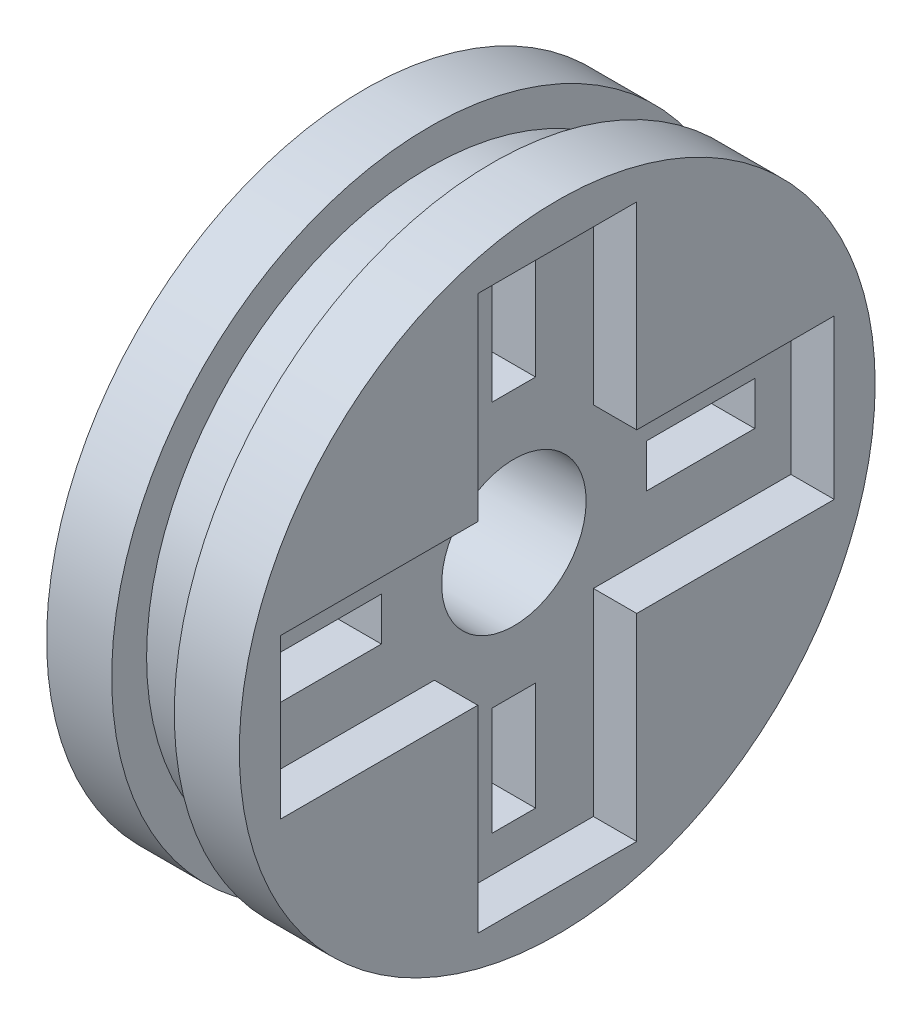
SolidWorks part; units mm, degrees
ref_plane "Front Plane" through (0, 0, 0) normal (0, 0, 1) x (1, 0, 0)
ref_plane "Top Plane" through (0, 0, 0) normal (0, 1, 0) x (1, 0, 0)
ref_plane "Right Plane" through (0, 0, 0) normal (1, 0, 0) x (0, 0, -1)
sketch "Sketch1" plane through (0, 0, 0) normal (1, 0, 0) x (0, 0, -1)
  circle A0 centre (52, -65) radius 13.2
extrude "Boss-Extrude1" add sketch "Sketch1" along normal blind 8 from offset 85.2 offset against normal yes
sketch "Sketch2" plane through (0, 0, 0) normal (1, 0, 0) x (0, 0, -1)
  circle A0 centre (52, -65) radius 20
extrude "Boss-Extrude2" add sketch "Sketch2" along normal blind 2.6 from offset 82.5 separate body offset against normal yes
combine bodies "Combine1" operation type subtract main body 101 bodies to subtract 102
sketch "Sketch3" plane through (0, 0, 0) normal (1, 0, 0) x (0, 0, -1)
  circle A0 centre (52, -65) radius 11.75
extrude "Boss-Extrude3" add sketch "Sketch3" along normal blind 2.6 from offset 82.5 offset against normal yes
sketch "Sketch4" plane through (0, 0, 0) normal (1, 0, 0) x (0, 0, -1)
  circle A0 centre (52, -65) radius 4.6
extrude "Boss-Extrude4" add sketch "Sketch4" along normal blind 2.3 from offset 79 separate body offset against normal yes
combine bodies "Combine2" operation type subtract main body 105 bodies to subtract 106
sketch "Sketch5" plane through (0, 0, 0) normal (0, 0, 1) x (1, 0, 0)
  line L1 (-79, -65) -> (-76.7, -65)
  line L2 (-79, -65) -> (-79, -53.5)
  line L3 (-79, -53.5) -> (-76.7, -53.5)
  line L4 (-76.7, -65) -> (-76.7, -53.5)
extrude "Boss-Extrude5" add sketch "Sketch5" along normal blind 6.6 from offset 55.3 separate body offset against normal yes
combine bodies "Combine3" operation type subtract main body 107 bodies to subtract 108
sketch "Sketch6" plane through (0, 0, 0) normal (0, 0, 1) x (1, 0, 0)
  line L1 (-86.2, -59.5) -> (-76.2, -59.5)
  line L2 (-86.2, -59.5) -> (-86.2, -55)
  line L3 (-86.2, -55) -> (-76.2, -55)
  line L4 (-76.2, -59.5) -> (-76.2, -55)
extrude "Boss-Extrude6" add sketch "Sketch6" along normal blind 1.8 from offset 52.9 separate body offset against normal yes
combine bodies "Combine4" operation type subtract main body 109 bodies to subtract 110
sketch "Sketch7" plane through (0, 0, 0) normal (0, 0, 1) x (1, 0, 0)
  line L1 (-79, -76.5) -> (-76.7, -76.5)
  line L2 (-79, -76.5) -> (-79, -65)
  line L3 (-79, -65) -> (-76.7, -65)
  line L4 (-76.7, -76.5) -> (-76.7, -65)
extrude "Boss-Extrude7" add sketch "Sketch7" along normal blind 6.6 from offset 55.3 separate body offset against normal yes
combine bodies "Combine5" operation type subtract main body 111 bodies to subtract 112
sketch "Sketch8" plane through (0, 0, 0) normal (0, 0, 1) x (1, 0, 0)
  line L1 (-86.2, -75) -> (-76.2, -75)
  line L2 (-86.2, -75) -> (-86.2, -70.5)
  line L3 (-86.2, -70.5) -> (-76.2, -70.5)
  line L4 (-76.2, -75) -> (-76.2, -70.5)
extrude "Boss-Extrude8" add sketch "Sketch8" along normal blind 1.8 from offset 52.9 separate body offset against normal yes
combine bodies "Combine6" operation type subtract main body 113 bodies to subtract 114
sketch "Sketch9" plane through (0, 0, 0) normal (0, 0, 1) x (1, 0, 0)
  line L1 (-79, -68.3) -> (-76.7, -68.3)
  line L2 (-79, -68.3) -> (-79, -61.7)
  line L3 (-79, -61.7) -> (-76.7, -61.7)
  line L4 (-76.7, -68.3) -> (-76.7, -61.7)
extrude "Boss-Extrude9" add sketch "Sketch9" along normal blind 11.5 from offset 52 separate body offset against normal yes
combine bodies "Combine7" operation type subtract main body 115 bodies to subtract 116
sketch "Sketch10" plane through (0, 0, 0) normal (0, 0, 1) x (1, 0, 0)
  line L1 (-86.2, -65.9) -> (-76.2, -65.9)
  line L2 (-86.2, -65.9) -> (-86.2, -64.1)
  line L3 (-86.2, -64.1) -> (-76.2, -64.1)
  line L4 (-76.2, -65.9) -> (-76.2, -64.1)
extrude "Boss-Extrude10" add sketch "Sketch10" along normal blind 4.5 from offset 46.5 separate body offset against normal yes
combine bodies "Combine8" operation type subtract main body 117 bodies to subtract 118
sketch "Sketch11" plane through (0, 0, 0) normal (0, 0, 1) x (1, 0, 0)
  line L1 (-79, -68.3) -> (-76.7, -68.3)
  line L2 (-79, -68.3) -> (-79, -61.7)
  line L3 (-79, -61.7) -> (-76.7, -61.7)
  line L4 (-76.7, -68.3) -> (-76.7, -61.7)
extrude "Boss-Extrude11" add sketch "Sketch11" along normal blind 11.5 from offset 63.5 separate body offset against normal yes
combine bodies "Combine9" operation type subtract main body 119 bodies to subtract 120
sketch "Sketch12" plane through (0, 0, 0) normal (0, 0, 1) x (1, 0, 0)
  line L1 (-86.2, -65.9) -> (-76.2, -65.9)
  line L2 (-86.2, -65.9) -> (-86.2, -64.1)
  line L3 (-86.2, -64.1) -> (-76.2, -64.1)
  line L4 (-76.2, -65.9) -> (-76.2, -64.1)
extrude "Boss-Extrude12" add sketch "Sketch12" along normal blind 4.5 from offset 62 separate body offset against normal yes
combine bodies "Combine10" operation type subtract main body 121 bodies to subtract 122
sketch "Sketch13" plane through (0, 0, 0) normal (1, 0, 0) x (0, 0, -1)
  circle A0 centre (52, -65) radius 3
extrude "Boss-Extrude13" add sketch "Sketch13" along normal blind 10 from offset 86.2 separate body offset against normal yes
combine bodies "Combine11" operation type subtract main body 123 bodies to subtract 124
